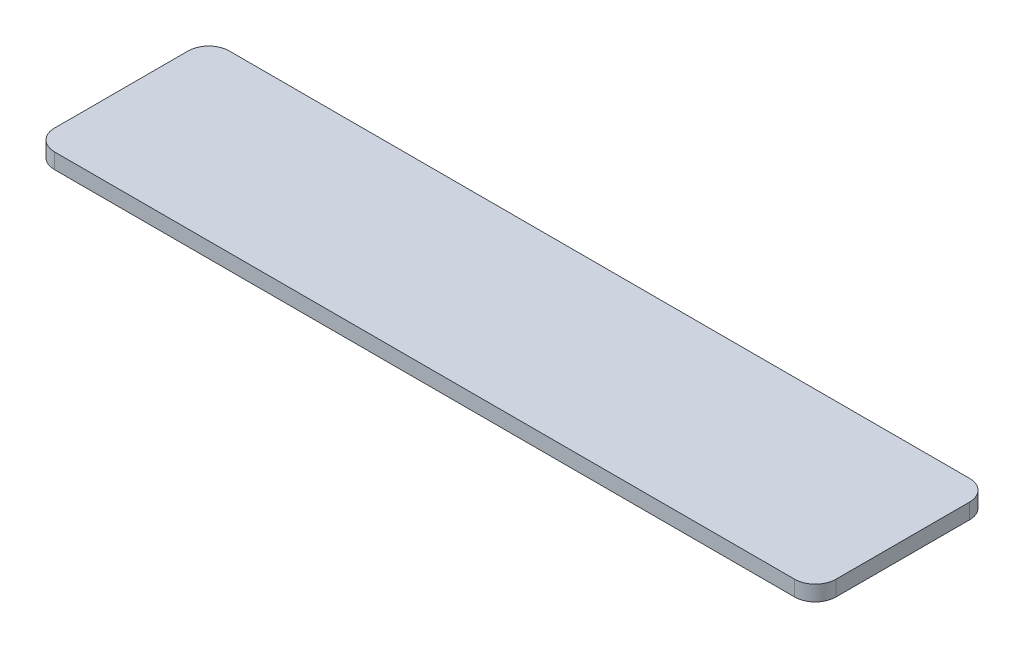
SolidWorks part; units mm, degrees
material "ASTM A36 Steel"
ref_plane "Front Plane" through (0, 0, 0) normal (0, 0, 1) x (1, 0, 0)
ref_plane "Top Plane" through (0, 0, 0) normal (0, 1, 0) x (1, 0, 0)
ref_plane "Right Plane" through (0, 0, 0) normal (1, 0, 0) x (0, 0, -1)
sketch "Sketch1" plane through (0, 0, 0) normal (0, 1, 0) x (1, 0, 0)
  line L1 (-241.3, -53.975) -> (241.3, -53.975)
  line L2 (-241.3, -53.975) -> (-241.3, 53.975)
  line L3 (-241.3, 53.975) -> (241.3, 53.975)
  line L4 (241.3, -53.975) -> (241.3, 53.975)
  line L5 (-241.3, -53.975) -> (241.3, 53.975) construction
  line L6 (-241.3, 53.975) -> (241.3, -53.975) construction
  point P0 (0, 0)
  dimension "D1" = 482.6
  dimension "D2" = 107.95
base flange "Base-Flange1" sketch "Sketch1" thickness 9.525 reverse thickness direction no parameters "D1"=6.3754
fillet "Fillet1" radius 12.7 4 edges at (241.3, -4.7625, -53.975) (-241.3, -4.7625, -53.975) (-241.3, -4.7625, 53.975) (241.3, -4.7625, 53.975)
sketch "Bend-Lines1" [suppressed] plane through (0, 0, 0) normal (0, 1, 0) x (1, 0, 0)
sketch "Bounding-Box1" [suppressed] plane through (0, 0, 0) normal (0, 1, 0) x (1, 0, 0)
sheet metal parameters "Sheet-Metal4" thickness 9.525 parameters "D1"=6.3754
flat pattern "Flat-Pattern4" [suppressed]
sketch "Bend-Lines2" plane through (0, 0, 0) normal (0, 1, 0) x (1, 0, 0)
sketch3d "Bounding-Box2" [suppressed]
  line L0 (-241.3, 53.975, 0) -> (241.3, 53.975, 0) construction
  line L1 (-241.3, -53.975, 0) -> (241.3, -53.975, 0) construction
  line L2 (-241.3, 53.975, 0) -> (-241.3, -53.975, 0) construction
  line L3 (241.3, 53.975, 0) -> (241.3, -53.975, 0) construction
equation "\"PRIMER_USAGE\"= ( \"SW-SurfaceArea\" / 144 ) / 135"
equation "\"WET_PAINT_USAGE\"= ( \"SW-SurfaceArea\" / 144 ) / 125"
equation "\"POWDERCOAT_USAGE\"= ( \"SW-SurfaceArea\" / 144 ) / 29.79"
equation "\"DECKOVER_USAGE\"= ( \"SW-SurfaceArea\" / 144 ) / 75"
equation "\"SW_NON-SKID\"= ( \"SW-SurfaceArea\" / 144 ) / 165"
equation "\"TYPE_1_ANODIZATING\"= ( \"SW-SurfaceArea\" * 0.0001 )"
equation "\"TYPE_2_ANODIZING\"= ( \"SW-SurfaceArea\" * 0.0005 )"
equation "\"TYPE_3_ANODIZING-HARDCOAT\"= ( \"SW-SurfaceArea\" * 0.003 )"
